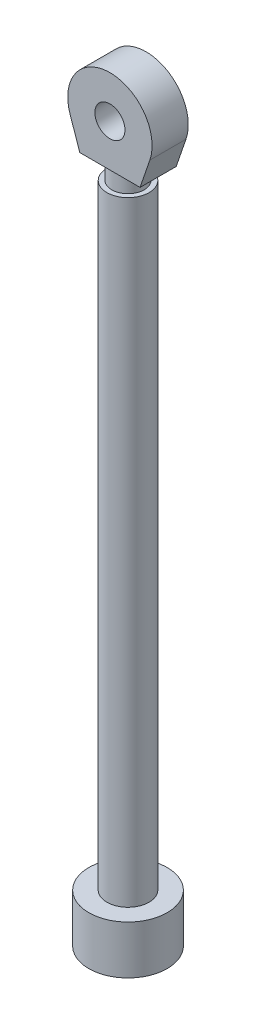
SolidWorks part; units mm, degrees
material "Plain Carbon Steel"
ref_plane "Front Plane" through (0, 0, 0) normal (0, 0, 1) x (1, 0, 0)
ref_plane "Top Plane" through (0, 0, 0) normal (0, 1, 0) x (1, 0, 0)
ref_plane "Right Plane" through (0, 0, 0) normal (1, 0, 0) x (0, 0, -1)
sketch "Sketch1" plane through (0, 0, 0) normal (0, 0, 1) x (1, 0, 0)
  line L0 (-17.5, -50) -> (-17.5, -550) construction
  line L1 (-17.5, -50) -> (17.5, -50) construction
  line L2 (-17.5, -550) -> (17.5, -550) construction
  line L3 (17.5, -50) -> (17.5, -550) construction
  line L4 (-32.5, -550) -> (32.5, -550) construction
  line L5 (-32.5, -550) -> (-32.5, -590.2222) construction
  line L6 (32.5, -550) -> (32.5, -590.2222) construction
  line L7 (-32.5, -590.2222) -> (32.5, -590.2222) construction
  line L8 (0, -550) -> (0, -50) construction
  line L9 (0, -550) -> (0, -590.2222) construction
  line L10 (-13.5, -50) -> (13.5, -50) construction
  line L11 (-13.5, -50) -> (-13.5, -35) construction
  line L12 (13.5, -50) -> (13.5, -35) construction
  line L13 (-13.5, -35) -> (13.5, -35) construction
  line L14 (0, -35) -> (0, -50) construction
  line L15 (-25, -35) -> (25, -35) construction
  line L16 (-25, -35) -> (-33.1081, -11.3514) construction
  line L17 (33.1081, -11.3514) -> (25, -35) construction
  line L18 (0, -35) -> (0, 35) construction
  line L19 (-33.1081, -11.3514) -> (33.1081, -11.3514) construction
  line L20 (-25, -35) -> (25, -35)
  line L21 (25, -35) -> (33.1081, -11.3514)
  line L22 (-33.1081, -11.3514) -> (-25, -35)
  arc A0 (-33.1081, -11.3514) -> (33.1081, -11.3514) centre (0, 0) cw construction
  circle A1 centre (0, 0) radius 12.5 construction
  arc A2 (33.1081, -11.3514) -> (-33.1081, -11.3514) centre (0, 0) ccw
  circle A3 centre (0, 0) radius 12.5
  dimension "D4" = 35
  dimension "D7" = 25
  dimension "D1" = 65
  dimension "D2" = 35
  dimension "D3" = 4
  dimension "D5" = 50
  dimension "D6" = 35
  dimension "D8" = 15
  dimension "D9" = 550
extrude "Boss-Extrude1" add sketch "Sketch1" along normal mid plane 30
sketch "Sketch2" plane through (0, 0, 0) normal (0, 0, 1) x (1, 0, 0)
  line L0 (0, -35) -> (13.5, -35)
  line L1 (13.5, -35) -> (13.5, -50)
  line L2 (13.5, -50) -> (17.5, -50)
  line L3 (17.5, -50) -> (17.5, -560)
  line L4 (17.5, -560) -> (32.5, -560)
  line L5 (32.5, -560) -> (32.5, -600.2222)
  line L6 (32.5, -600.2222) -> (0, -600.2222)
  line B0 (0, -560) -> (0, -50) construction
sketch_block_instance "Cyl_rod-3"
sketch_block "Cyl_rod" parameters "D4"=35, "D7"=25, "D1"=65, "D2"=35, "D3"=4, "D5"=50, "D6"=35, "D8"=15, "D9"=560
revolve "Revolve-Thin1" add sketch "Sketch2" angle 360 about L8
